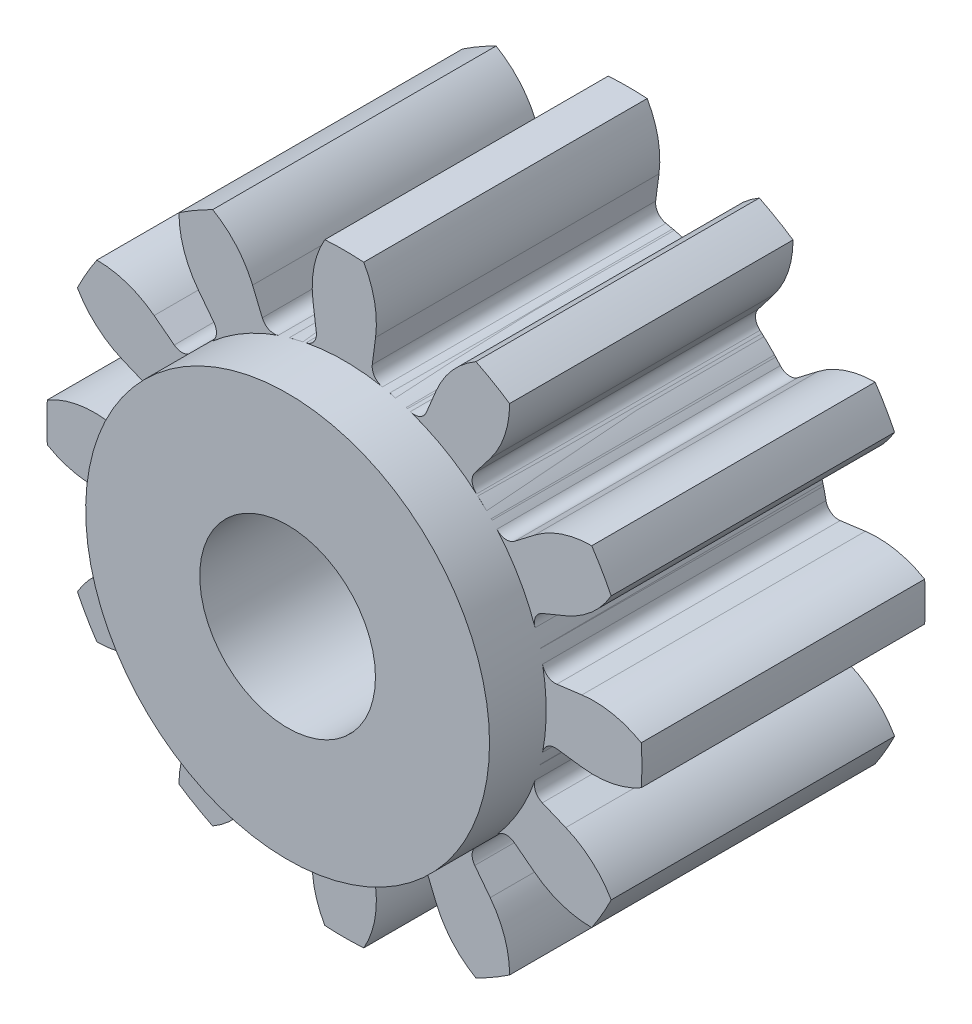
SolidWorks part; units mm, degrees
ref_plane "Front Plane" through (0, 0, 0) normal (0, 0, 1) x (1, 0, 0)
ref_plane "Top Plane" through (0, 0, 0) normal (0, 1, 0) x (1, 0, 0)
ref_plane "Right Plane" through (0, 0, 0) normal (1, 0, 0) x (0, 0, -1)
sketch "Esquisse1" plane through (0, 0, 0) normal (0, 0, 1) x (1, 0, 0)
  line L0 (0, 0) -> (22.1157, 0) construction
  line L1 (0, 0) -> (24.1492, 6.4708) construction
  line L2 (0, 0) -> (24.1492, -6.4708) construction
  line L3 (0, 0) -> (24.9429, 3.2838) construction
  line L4 (0, 0) -> (6.8822, 1.8441)
  line L5 (0, 0) -> (19.7164, -2.5957) construction
  line L6 (0, 0) -> (6.8822, -1.8441)
  line L7 (0, 0) -> (17.7915, 1.1661) construction
  line L8 (7.064, 0.93) -> (8.3849, 1.1039)
  line L9 (7.064, -0.93) -> (8.3849, -1.1039)
  line L10 (0, 0) -> (17.695, -1.1598) construction
  circle A0 centre (0, 0) radius 9 construction
  circle A1 centre (0, 0) radius 10.5 construction
  circle A2 centre (0, 0) radius 7.125 construction
  circle A3 centre (0, 0) radius 8.4572 construction
  arc A4 (6.8822, 1.8441) -> (7.064, 0.93) centre (0, 0) cw
  arc A5 (6.8822, -1.8441) -> (7.064, -0.93) centre (0, 0) ccw
  arc A6 (8.3849, 1.1039) -> (10.4775, 0.6867) centre (8.8176, -2.1828) cw
  arc A7 (10.4775, 0.6867) -> (10.4775, -0.6867) centre (0, 0) cw
  arc A8 (8.3849, -1.1039) -> (10.4775, -0.6867) centre (8.8176, 2.1828) ccw
  dimension "PrimitiveDiameter" = 18
  dimension "OutsideDiameter" = 21
  dimension "InternalDiameter" = 14.25
  dimension "BaseDiameter" = 16.9145
  dimension "DemiToothAngle" = 15
  dimension "QuartToothAngle" = 7.5
  dimension "D1" = 7.5
  dimension "D2" = 3.75
  dimension "D3" = 3.75
extrude "MainGear" add sketch "Esquisse1" along normal blind 10
fillet "Congé1" radius 0.45 2 edges at (7.064, -0.93, 5) (7.064, 0.93, 5)
ref_axis "Axe1" through (0, 0, 10) along (0, 0, -1)
pattern_circular "Répétition circulaire1" count 12 every 30 about axis through (0, 0, 10) along (0, 0, -1) of "MainGear", "Congé1"
sketch "Esquisse3" plane through (0, 0, 0) normal (0, 0, 1) x (1, 0, 0)
  circle A0 centre (0, 0) radius 3.1
  dimension "D1" = 6.2
sketch "Esquisse5" plane through (0, 0, 10) normal (0, 0, 1) x (1, 0, 0)
  circle A0 centre (0, 0) radius 7.125
extrude "MainBaseCircle" add sketch "Esquisse5" against normal through all
sketch "Esquisse9" plane through (0, 0, 10) normal (0, 0, 1) x (1, 0, 0)
  circle A0 centre (0, 0) radius 7.125
  circle A1 centre (0, 0) radius 7.125 construction
  circle A2 centre (0, 0) radius 3.1
  dimension "D1" = 6.2
extrude "GearBottomFix" add sketch "Esquisse9" along normal blind 2
extrude "GearHole" cut sketch "Esquisse3" along normal through all
equation "\"Modulo\"= 1.5mm"
equation "\"ToothCount\"= 12"
equation "\"PrimitiveDiameter@Esquisse1\"= \"Modulo\" * \"ToothCount\""
equation "\"OutsideDiameter@Esquisse1\" = \"Modulo\" *  ( \"ToothCount\" + 2 ) "
equation "\"InternalDiameter@Esquisse1\" = \"PrimitiveDiameter@Esquisse1\" - \"Modulo\" * 2.5"
equation "\"Angle\"= 20deg"
equation "\"BaseDiameter@Esquisse1\" = \"PrimitiveDiameter@Esquisse1\" * cos ( \"Angle\" ) "
equation "\"DemiToothAngle@Esquisse1\" = 180 / \"ToothCount\""
equation "\"QuartToothAngle@Esquisse1\"= \"DemiToothAngle@Esquisse1\" / 2"
equation "\"D1@Esquisse1\"= \"QuartToothAngle@Esquisse1\""
equation "\"D2@Esquisse1\"= \"QuartToothAngle@Esquisse1\" / 2"
equation "\"D3@Esquisse1\"= \"D2@Esquisse1\""
equation "\"D2@Répétition circulaire1\"=360/\"ToothCount\""
equation "\"D1@Congé1\"=\"Modulo\"*0.3"
